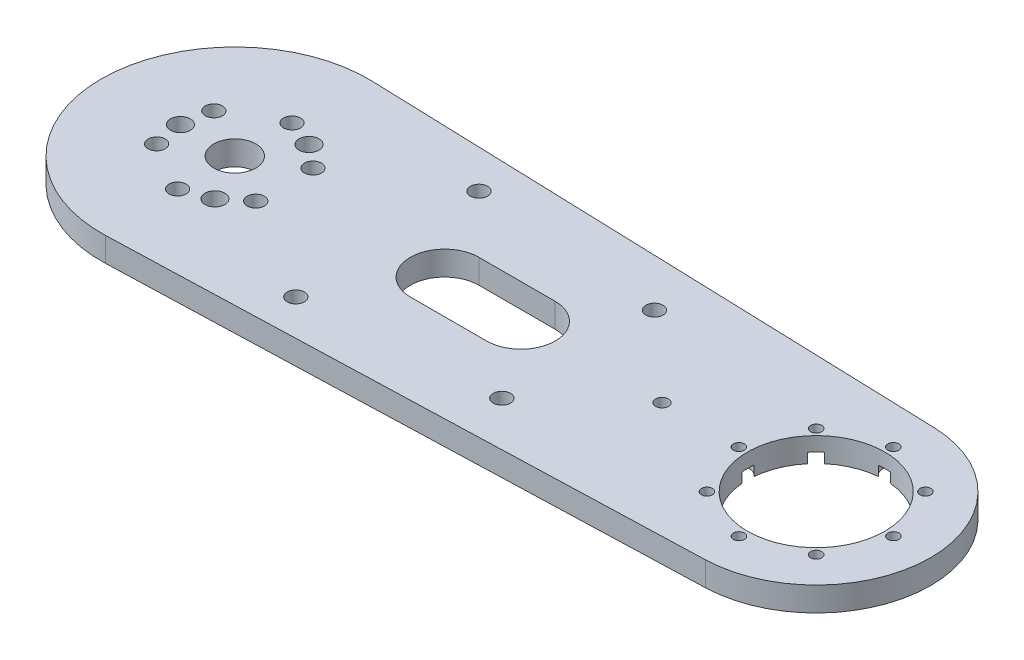
SolidWorks part; units mm, degrees
material "Aleación 6061"
ref_plane "Alzado" through (0, 0, 0) normal (0, 0, 1) x (1, 0, 0)
ref_plane "Planta" through (0, 0, 0) normal (0, 1, 0) x (1, 0, 0)
ref_plane "Vista lateral" through (0, 0, 0) normal (1, 0, 0) x (0, 0, -1)
ref_plane "Plano_zJ2" through (0, 0, 171.45) normal (0, 0, 1) x (1, 0, 0)
ref_plane "Plano_xJ3" through (152.4, 0, 0) normal (1, 0, 0) x (0, 0, -1)
ref_axis "Eje_J2" through (0, -3.4925, 171.45) along (0, 1, 0)
ref_axis "Eje_J3" through (152.4, -3.4925, 171.45) along (0, 1, 0)
sketch "Croquis13" plane through (0, 0, 0) normal (0, 1, 0) x (1, 0, 0)
  line L0 (1.1483, -206.4312) -> (153.3843, -201.4338)
  line L1 (153.3843, -201.4338) -> (153.3843, -141.4662)
  line L2 (153.3843, -141.4662) -> (1.1483, -136.4688)
  line L3 (1.1483, -136.4688) -> (1.1483, -206.4312)
  dimension "D1" = 1.1483
  dimension "D2" = 206.4312
  dimension "D3" = 153.3843
  dimension "D4" = 201.4338
  dimension "D5" = 153.3843
  dimension "D6" = 141.4662
  dimension "D7" = 1.1483
  dimension "D8" = 136.4688
extrude "Placa" add sketch "Croquis13" along normal blind 6.35 from offset 4
sketch "Croquis14" plane through (0, 0, 0) normal (0, 1, 0) x (1, 0, 0)
  circle A0 centre (0, -171.45) radius 35
  dimension "D1" = 70
  dimension "D2" = 171.45
extrude "Placa_r1" add sketch "Croquis14" along normal blind 6.35 from offset 4
sketch "Croquis15" plane through (0, 0, 0) normal (0, 1, 0) x (1, 0, 0)
  circle A0 centre (152.4, -171.45) radius 30
  dimension "D1" = 60
  dimension "D2" = 152.4
  dimension "D3" = 171.45
extrude "Placa_r2" add sketch "Croquis15" along normal blind 6.35 from offset 4
sketch "Croquis16" plane through (0, 0, 0) normal (0, 1, 0) x (1, 0, 0)
  line L0 (55, -162.45) -> (75, -162.45)
  line L1 (75, -180.45) -> (55, -180.45)
  arc A0 (75, -162.45) -> (75, -180.45) centre (75, -171.45) cw
  arc A1 (55, -180.45) -> (55, -162.45) centre (55, -171.45) cw
  dimension "D1" = 9
  dimension "D2" = 9
  dimension "D3" = 55
  dimension "D4" = 162.45
  dimension "D5" = 75
  dimension "D6" = 162.45
  dimension "D7" = 75
  dimension "D8" = 180.45
  dimension "D9" = 55
  dimension "D10" = 180.45
extrude "Aligerado" cut sketch "Croquis16" along normal blind 6.35 from offset 4
sketch "Croquis17" plane through (0, 0, 0) normal (0, 1, 0) x (1, 0, 0)
  circle A0 centre (40, -195.45) radius 2.25
  circle A1 centre (40, -147.45) radius 2.25
  circle A2 centre (90, -191.45) radius 2.25
  circle A3 centre (90, -151.45) radius 2.25
  dimension "D1" = 4.5
  dimension "D2" = 4.5
  dimension "D3" = 4.5
  dimension "D4" = 4.5
  dimension "D5" = 40
  dimension "D6" = 195.45
  dimension "D7" = 40
  dimension "D8" = 147.45
  dimension "D9" = 90
  dimension "D10" = 191.45
  dimension "D11" = 90
  dimension "D12" = 151.45
extrude "Barrenos_separadores_M4" cut sketch "Croquis17" along normal blind 6.35 from offset 4
sketch "Croquis18" plane through (0, 0, 0) normal (0, 1, 0) x (1, 0, 0)
  circle A0 centre (12.9904, -178.95) radius 2.25
  circle A1 centre (0, -186.45) radius 2.25
  circle A2 centre (-12.9904, -178.95) radius 2.25
  circle A3 centre (-12.9904, -163.95) radius 2.25
  circle A4 centre (0, -156.45) radius 2.25
  circle A5 centre (12.9904, -163.95) radius 2.25
  circle A6 centre (7.125, -183.7909) radius 2.6
  circle A7 centre (-14.25, -171.45) radius 2.6
  circle A8 centre (7.125, -159.1091) radius 2.6
  circle A9 centre (0, -171.45) radius 5.5
  circle A10 centre (152.4, -171.45) radius 18
  circle A11 centre (172.65, -171.45) radius 1.45
  circle A12 centre (166.7189, -185.7689) radius 1.45
  circle A13 centre (152.4, -191.7) radius 1.45
  circle A14 centre (138.0811, -185.7689) radius 1.45
  circle A15 centre (132.15, -171.45) radius 1.45
  circle A16 centre (138.0811, -157.1311) radius 1.45
  circle A17 centre (152.4, -151.2) radius 1.45
  circle A18 centre (166.7189, -157.1311) radius 1.45
  dimension "D1" = 4.5
  dimension "D2" = 4.5
  dimension "D3" = 4.5
  dimension "D4" = 4.5
  dimension "D5" = 4.5
  dimension "D6" = 4.5
  dimension "D7" = 5.2
  dimension "D8" = 5.2
  dimension "D9" = 5.2
  dimension "D10" = 11
  dimension "D11" = 36
  dimension "D12" = 2.9
  dimension "D13" = 2.9
  dimension "D14" = 2.9
  dimension "D15" = 2.9
  dimension "D16" = 2.9
  dimension "D17" = 2.9
  dimension "D18" = 2.9
  dimension "D19" = 2.9
  dimension "D20" = 12.9904
  dimension "D21" = 178.95
  dimension "D22" = 186.45
  dimension "D23" = 12.9904
  dimension "D24" = 178.95
  dimension "D25" = 12.9904
  dimension "D26" = 163.95
  dimension "D27" = 156.45
  dimension "D28" = 12.9904
  dimension "D29" = 163.95
  dimension "D30" = 7.125
  dimension "D31" = 183.7909
  dimension "D32" = 14.25
  dimension "D33" = 171.45
  dimension "D34" = 7.125
  dimension "D35" = 159.1091
  dimension "D36" = 171.45
  dimension "D37" = 152.4
  dimension "D38" = 171.45
  dimension "D39" = 172.65
  dimension "D40" = 171.45
  dimension "D41" = 166.7189
  dimension "D42" = 185.7689
  dimension "D43" = 152.4
  dimension "D44" = 191.7
  dimension "D45" = 138.0811
  dimension "D46" = 185.7689
  dimension "D47" = 132.15
  dimension "D48" = 171.45
  dimension "D49" = 138.0811
  dimension "D50" = 157.1311
  dimension "D51" = 152.4
  dimension "D52" = 151.2
  dimension "D53" = 166.7189
  dimension "D54" = 157.1311
extrude "Barrenos_M2_y_M3" cut sketch "Croquis18" along normal blind 6.35 from offset 4
sketch "Croquis19" plane through (0, 0, 0) normal (0, 1, 0) x (1, 0, 0)
  circle A0 centre (12.9904, -178.95) radius 4
  circle A1 centre (0, -186.45) radius 4
  circle A2 centre (-12.9904, -178.95) radius 4
  circle A3 centre (-12.9904, -163.95) radius 4
  circle A4 centre (0, -156.45) radius 4
  circle A5 centre (12.9904, -163.95) radius 4
  dimension "D1" = 8
  dimension "D2" = 8
  dimension "D3" = 8
  dimension "D4" = 8
  dimension "D5" = 8
  dimension "D6" = 8
  dimension "D7" = 12.9904
  dimension "D8" = 178.95
  dimension "D9" = 186.45
  dimension "D10" = 12.9904
  dimension "D11" = 178.95
  dimension "D12" = 12.9904
  dimension "D13" = 163.95
  dimension "D14" = 156.45
  dimension "D15" = 12.9904
  dimension "D16" = 163.95
extrude "Refrentado_M4_cabeza_baja" cut sketch "Croquis19" along normal blind 2.8 from offset 4
sketch "Croquis20" plane through (0, 0, 0) normal (0, 1, 0) x (1, 0, 0)
  circle A0 centre (172.65, -171.45) radius 2.8
  circle A1 centre (166.7189, -185.7689) radius 2.8
  circle A2 centre (152.4, -191.7) radius 2.8
  circle A3 centre (138.0811, -185.7689) radius 2.8
  circle A4 centre (132.15, -171.45) radius 2.8
  circle A5 centre (138.0811, -157.1311) radius 2.8
  circle A6 centre (152.4, -151.2) radius 2.8
  circle A7 centre (166.7189, -157.1311) radius 2.8
  dimension "D1" = 5.6
  dimension "D2" = 5.6
  dimension "D3" = 5.6
  dimension "D4" = 5.6
  dimension "D5" = 5.6
  dimension "D6" = 5.6
  dimension "D7" = 5.6
  dimension "D8" = 5.6
  dimension "D9" = 172.65
  dimension "D10" = 171.45
  dimension "D11" = 166.7189
  dimension "D12" = 185.7689
  dimension "D13" = 152.4
  dimension "D14" = 191.7
  dimension "D15" = 138.0811
  dimension "D16" = 185.7689
  dimension "D17" = 132.15
  dimension "D18" = 171.45
  dimension "D19" = 138.0811
  dimension "D20" = 157.1311
  dimension "D21" = 152.4
  dimension "D22" = 151.2
  dimension "D23" = 166.7189
  dimension "D24" = 157.1311
extrude "Refrentado_M2-5" cut sketch "Croquis20" along normal blind 2.6 from offset 4
sketch "Croquis21" plane through (0, 0, 0) normal (0, 1, 0) x (1, 0, 0)
  circle A0 centre (112, -171.45) radius 1.25
  dimension "D1" = 2.5
  dimension "D2" = 112
  dimension "D3" = 171.45
extrude "Rosca_M3_bases_cincho" cut sketch "Croquis21" along normal blind 6.35 from offset 4
sketch "Croquis22" plane through (0, 0, 0) normal (0, 1, 0) x (1, 0, 0)
  circle A0 centre (112, -171.45) radius 1.7
  dimension "D1" = 3.4
  dimension "D2" = 112
  dimension "D3" = 171.45
extrude "Paso_M3_bases_cincho" cut sketch "Croquis22" along normal blind 6.35 from offset 4
